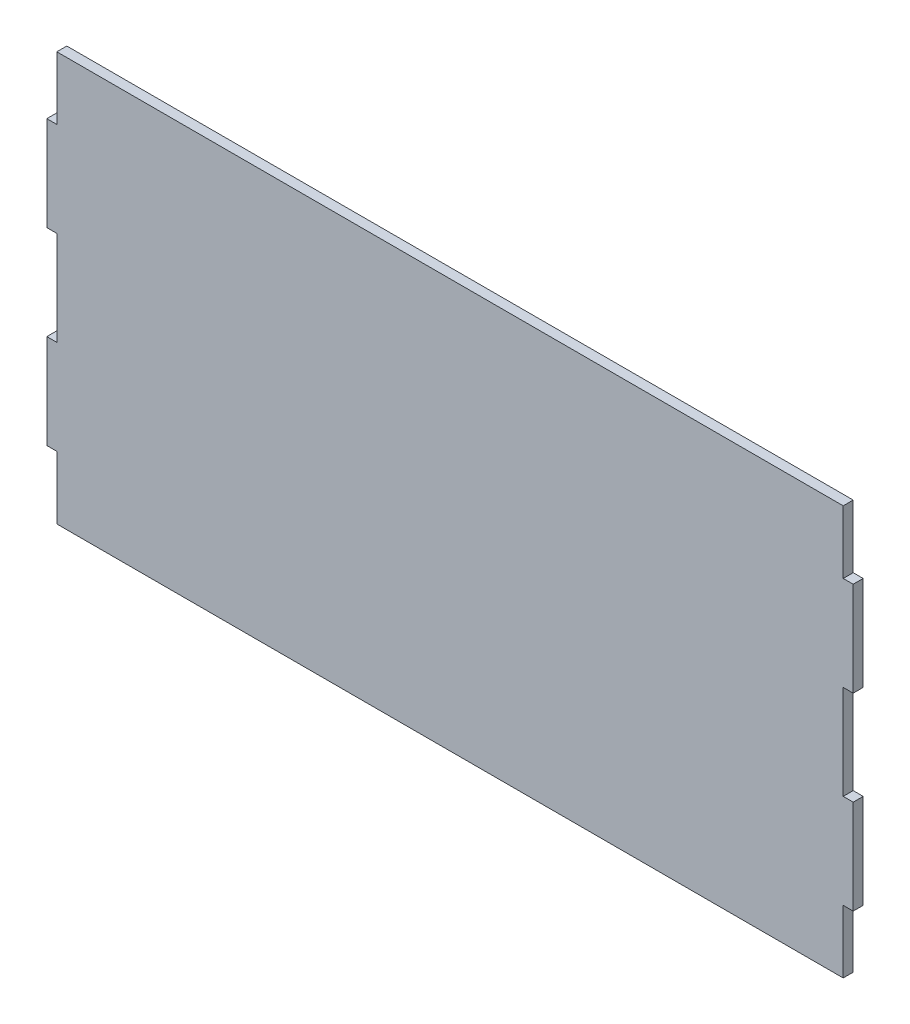
SolidWorks part; units mm, degrees
ref_plane "前视" through (0, 0, 0) normal (0, 0, 1) x (1, 0, 0)
ref_plane "上视" through (0, 0, 0) normal (0, 1, 0) x (1, 0, 0)
ref_plane "右视" through (0, 0, 0) normal (1, 0, 0) x (0, 0, -1)
sketch "Sketch1" plane through (0, 0, 0) normal (0, 0, 1) x (1, 0, 0)
  line L1 (0, 0) -> (250, 0)
  line L2 (0, 0) -> (0, -130)
  line L3 (0, -130) -> (250, -130)
  line L4 (250, 0) -> (250, -130)
  dimension "D1" = 250
  dimension "D2" = 130
extrude "Boss-Extrude1" add sketch "Sketch1" along normal blind 3.175
sketch "Sketch2" plane through (0, 0, 3.175) normal (0, 0, 1) x (1, 0, 0)
  line L0 (0, 0) -> (0, -130) construction
  line L1 (0, -20) -> (-3.175, -20)
  line L2 (0, -20) -> (0, -50)
  line L3 (0, -50) -> (-3.175, -50)
  line L4 (-3.175, -20) -> (-3.175, -50)
  line L5 (250, 0) -> (0, 0) construction
  line L6 (250, -130) -> (250, 0) construction
  line L7 (250, -20) -> (253.175, -20)
  line L8 (250, -20) -> (250, -50)
  line L9 (250, -50) -> (253.175, -50)
  line L10 (253.175, -20) -> (253.175, -50)
  line L11 (0, -80) -> (-3.175, -80)
  line L12 (-3.175, -80) -> (-3.175, -110)
  line L13 (0, -80) -> (0, -110)
  line L14 (0, -110) -> (-3.175, -110)
  line L15 (250, -80) -> (253.175, -80)
  line L16 (253.175, -80) -> (253.175, -110)
  line L17 (250, -80) -> (250, -110)
  line L18 (250, -110) -> (253.175, -110)
  dimension "D1" = 3.175
  dimension "D2" = 20
  dimension "D3" = 30
  dimension "D4" = 3.175
  dimension "D5" = 2
extrude "Boss-Extrude2" add sketch "Sketch2" against normal up to surface (3.175 mm away) up to face at (125, -65, 0)
